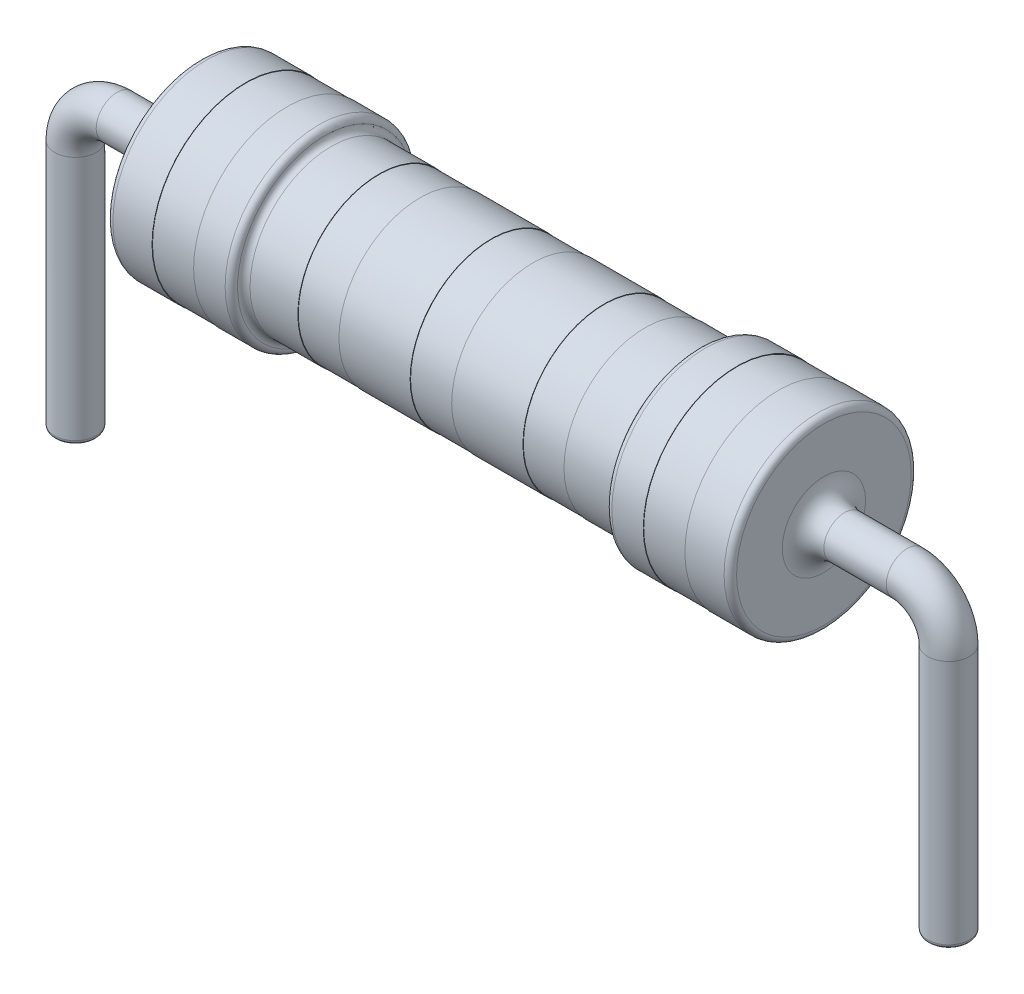
SolidWorks part; units mm, degrees
ref_plane "Front Plane" through (0, 0, 0) normal (0, 0, 1) x (1, 0, 0)
ref_plane "Top Plane" through (0, 0, 0) normal (0, 1, 0) x (1, 0, 0)
ref_plane "Right Plane" through (0, 0, 0) normal (1, 0, 0) x (0, 0, -1)
sketch "Sketch1" plane through (0, 0, 0) normal (0, 0, 1) x (1, 0, 0)
  line L0 (-7.5, -1.8974) -> (7.5, -1.8974)
  line L1 (7.5, -1.8974) -> (7.5, -4.1474)
  line L2 (7.5, -4.1474) -> (6.4068, -4.1474)
  line L3 (-7.5, -1.8974) -> (-7.5, -4.1474)
  line L4 (6.4068, -4.1474) -> (6.4068, -4.1374)
  line L5 (6.4068, -4.1374) -> (5.4068, -4.1374)
  line L6 (5.4068, -4.1374) -> (5.4068, -4.1474)
  line L7 (5.4068, -4.1474) -> (4.5, -4.1474)
  line L8 (4.5, -4.1474) -> (4.5, -3.8474)
  line L9 (4.5, -3.8474) -> (3.2, -3.8474)
  line L10 (3.2, -3.8474) -> (3.2, -3.8374)
  line L11 (3.2, -3.8374) -> (2.2127, -3.8374)
  line L12 (2.2127, -3.8374) -> (2.2127, -3.8474)
  line L13 (2.2127, -3.8474) -> (0.5, -3.8474)
  line L14 (0.5, -3.8474) -> (0.5, -3.8374)
  line L15 (0.5, -3.8374) -> (-0.5, -3.8374)
  line L16 (-0.5, -3.8474) -> (-0.5, -3.8374)
  line L17 (-2.2127, -3.8474) -> (-0.5, -3.8474)
  line L18 (-2.2127, -3.8374) -> (-2.2127, -3.8474)
  line L19 (-3.2, -3.8374) -> (-2.2127, -3.8374)
  line L20 (-3.2, -3.8474) -> (-3.2, -3.8374)
  line L21 (-4.5, -3.8474) -> (-3.2, -3.8474)
  line L22 (-4.5, -4.1474) -> (-4.5, -3.8474)
  line L23 (-5.4068, -4.1474) -> (-4.5, -4.1474)
  line L24 (-5.4068, -4.1374) -> (-5.4068, -4.1474)
  line L25 (-6.4068, -4.1374) -> (-5.4068, -4.1374)
  line L26 (-6.4068, -4.1474) -> (-6.4068, -4.1374)
  line L27 (-7.5, -4.1474) -> (-6.4068, -4.1474)
  line L28 (-7.5, -4.1474) -> (-7.5091, -4.1346)
  dimension "D2" = 3
  dimension "D3" = 1
  dimension "D4" = 2.25
  dimension "D5" = 0.01
  dimension "D7" = 0.01
  dimension "D8" = 0.3
  dimension "D9" = 0.01
  dimension "D10" = 0.01
revolve "Revolve2" add sketch "Sketch1" angle 360 about L0
sketch "Sketch3" plane through (7.5, 0, 0) normal (1, 0, 0) x (0, 0, -1)
  circle A0 centre (0, -1.8974) radius 0.5
sketch3d "3DSketch1"
  line L0 (7.5, -1.8974, 0) -> (9.5, -1.8974, 0)
  line L1 (10.5, -2.8974, 0) -> (10.5, -8.8974, 0)
  arc A0 (10.5, -2.8974, 0) -> (9.5, -1.8974, 0) centre (9.5, -2.8974, 0) ccw
  point P6 (10.5, -1.8974, 0)
  point P7 (9.5, -2.8974, 1)
  dimension "D3" = 1
  dimension "D1" = 3
  dimension "D2" = 7
sweep "Sweep1" add profiles "Sketch3" path "3DSketch1"
mirror "Mirror1" about plane through (0, 0, 0) normal (1, 0, 0) of "Sweep1"
fillet "Fillet1" radius 0.1 2 edges at (-10.5, -8.8974, -0.5) (10.5, -8.8974, -0.5)
fillet "Fillet2" radius 0.15 4 edges at (4.5, -1.8974, 2.25) (-4.5, -1.8974, 2.25) (-7.5, -1.8974, 2.25) (7.5, -1.8974, 2.25)
fillet "Fillet3" radius 0.15 2 edges at (4.5, -1.8974, 1.95) (-4.5, -1.8974, 1.95)
fillet "Fillet4" radius 0.5 2 edges at (-7.5, -1.8974, 0.5) (7.5, -1.8974, -0.5)
